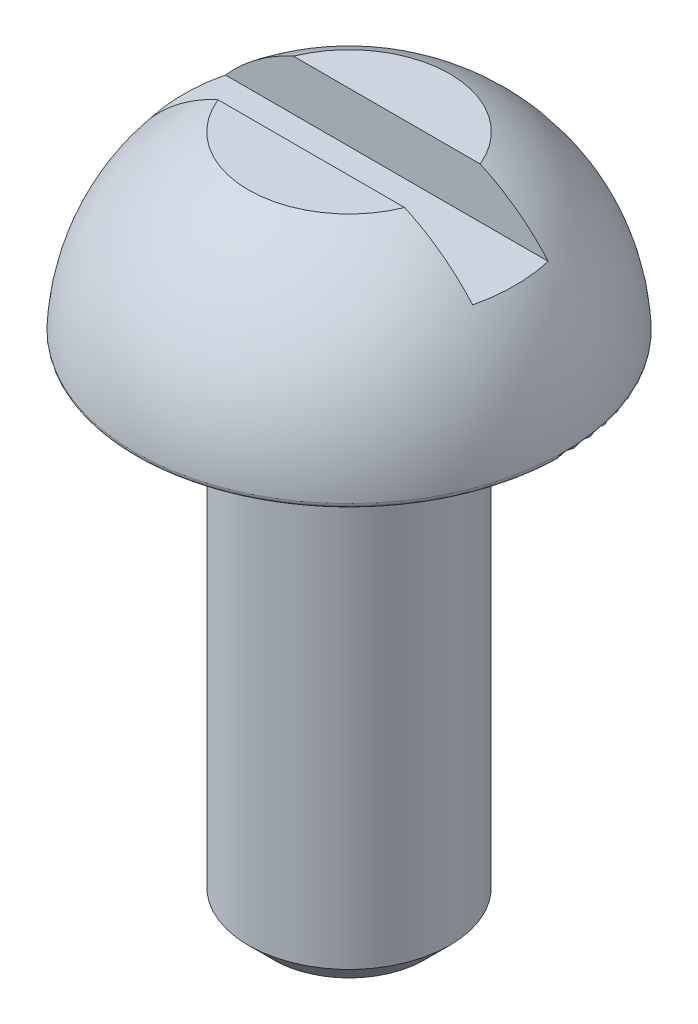
SolidWorks part; units mm, degrees
ref_plane "Спереди" through (0, 0, 0) normal (0, 0, 1) x (1, 0, 0)
ref_plane "Сверху" through (0, 0, 0) normal (0, 1, 0) x (1, 0, 0)
ref_plane "Справа" through (0, 0, 0) normal (1, 0, 0) x (0, 0, -1)
sketch "Эскиз1" plane through (0, 0, 0) normal (0, 0, 1) x (1, 0, 0)
  line L0 (4.25, 10) -> (2, 10)
  line L1 (0, 0) -> (0, 13.5)
  line L2 (2, 10) -> (2, 0.5)
  line L3 (2, 0.5) -> (1.5, 0)
  line L4 (1.5, 0) -> (0, 0)
  line L5 (0, 13.5) -> (2, 13.5)
  arc A0 (2, 13.5) -> (4.25, 10) centre (0.2512, 9.9025) cw
  point P9 (0, 0)
  dimension "D2" = 2
  dimension "D3" = 4
  dimension "D1" = 13.5
  dimension "D4" = 1.5
  dimension "D5" = 3.5
  dimension "D6" = 4.25
  dimension "D7" = 45
  dimension "D9" = 2
revolve "Повернуть1" add sketch "Эскиз1" angle 360 about L1
fillet "Скругление1" radius 0.1 1 edges at (0, 10, -4.25)
sketch "Эскиз3" plane through (0, 13.5, 0) normal (0, 1, 0) x (-1, 0, 0)
  line L1 (4, -0.75) -> (-4, -0.75)
  line L2 (4, -0.75) -> (4, 0.75)
  line L3 (4, 0.75) -> (-4, 0.75)
  line L4 (-4, -0.75) -> (-4, 0.75)
  dimension "D1" = 1.5
  dimension "D2" = 0.75
  dimension "D3" = 8
  dimension "D4" = 4
extrude "Вырез-Вытянуть2" cut sketch "Эскиз3" against normal blind 1
ref_axis "Ось1" through (0, -104.1565, 0) along (0, 1, 0)
